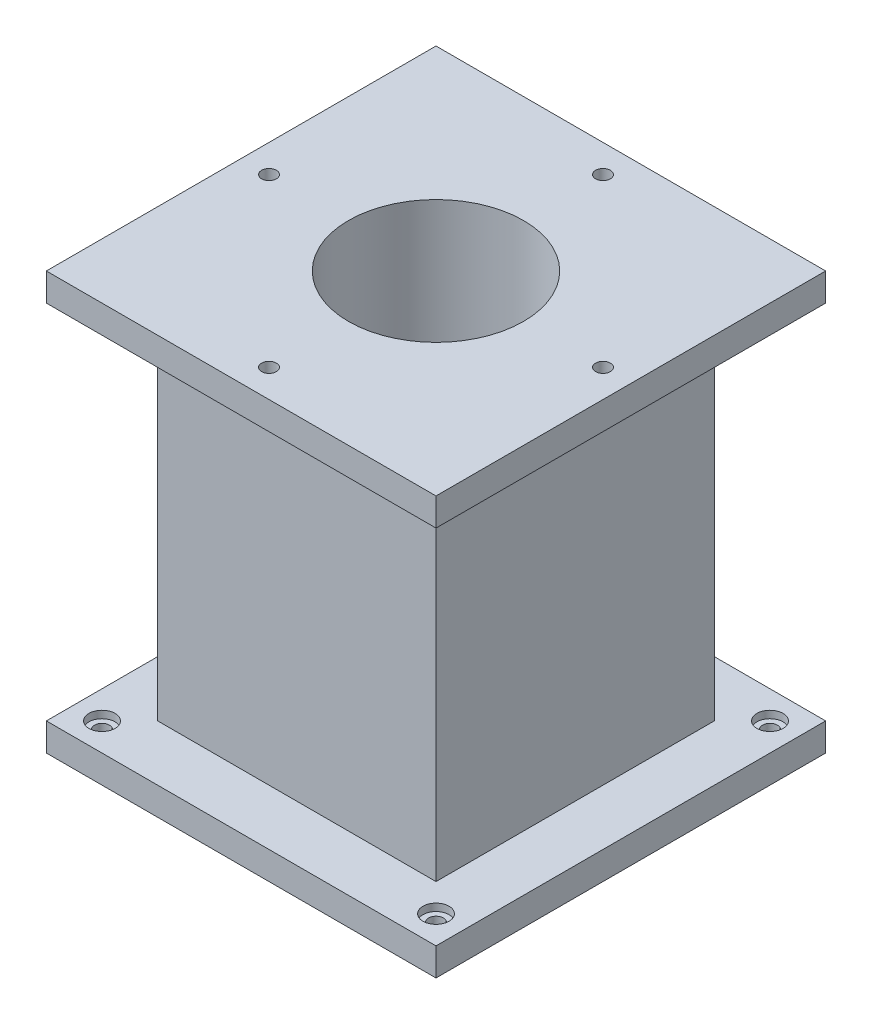
SolidWorks part; units mm, degrees
ref_plane "Front Plane" through (0, 0, 0) normal (0, 0, 1) x (1, 0, 0)
ref_plane "Top Plane" through (0, 0, 0) normal (0, 1, 0) x (1, 0, 0)
ref_plane "Right Plane" through (0, 0, 0) normal (1, 0, 0) x (0, 0, -1)
sketch "Sketch1" plane through (0, 0, 0) normal (0, 1, 0) x (1, 0, 0)
  line L1 (-88.9, -88.9) -> (88.9, -88.9)
  line L2 (-88.9, -88.9) -> (-88.9, 88.9)
  line L3 (-88.9, 88.9) -> (88.9, 88.9)
  line L4 (88.9, -88.9) -> (88.9, 88.9)
  line L5 (-88.9, -88.9) -> (88.9, 88.9) construction
  line L6 (-88.9, 88.9) -> (88.9, -88.9) construction
  point P0 (0, 0)
  dimension "D1" = 177.8
extrude "Boss-Extrude1" add sketch "Sketch1" along normal blind 12.7
sketch "Sketch2" plane through (0, 12.7, 0) normal (0, 1, 0) x (1, 0, 0)
  line L0 (88.9, 88.9) -> (-88.9, 88.9) construction
  line L1 (88.9, -88.9) -> (88.9, 88.9) construction
  point P0 (76.2, 76.2)
  dimension "D1" = 12.7
  dimension "D2" = 12.7
pattern_linear "LPattern1" count 2 spacing 177.8 along (0, 1, 0) of bodies 101 104
hole_wizard "CBORE for 1/4 Button Head Cap Screw1" positions "Sketch3" profile "Sketch5" counterbore size "1/4" standard "ANSI Inch" end condition through all
sketch "Sketch3" plane through (0, 12.7, 0) normal (0, 1, 0) x (1, 0, 0)
  point P0 (76.2, 76.2)
sketch "Sketch5" plane through (76.2, 12.7, -76.2) normal (1, 0, 0) x (0, 0, 1)
  line L0 (0, 0) -> (0, 12.7)
  line L1 (0, 12.7) -> (3.3782, 12.7)
  line L3 (3.3782, 12.7) -> (3.3782, 3.3528)
  line L4 (3.3782, 3.3528) -> (5.9538, 3.3528)
  line L5 (5.9538, 3.3528) -> (5.9538, 0)
  line L7 (5.9538, 0) -> (0, 0)
  line L11 (0, -6.35) -> (0, 107.95) construction
  dimension "Thru Hole Dia." = 6.7564
  dimension "Thru Hole Depth" = 12.7
  dimension "C'Bore Dia." = 11.9075
  dimension "C'Bore Depth" = 3.3528
ref_axis "Axis1" through (0, -0.635, 0) along (0, 1, 0)
pattern_circular "CirPattern1" count 4 over 360 about axis through (0, -0.635, 0) along (0, 1, 0) of "CBORE for 1/4 Button Head Cap Screw1"
sketch "Sketch6" plane through (0, 177.8, 0) normal (0, -1, 0) x (1, 0, 0)
  line L0 (88.9, 0) -> (46.7985, 0) construction
  line L1 (88.9, 88.9) -> (88.9, -88.9) construction
  point P0 (76.2, 0)
  dimension "D1" = 12.7
hole_wizard "CBORE for 1/4 Button Head Cap Screw2" positions "Sketch9" profile "Sketch10" counterbore size "1/4" standard "ANSI Inch" end condition through all
sketch "Sketch9" plane through (0, 177.8, 0) normal (0, -1, 0) x (-1, 0, 0)
  point P0 (-76.2, 0)
sketch "Sketch10" plane through (76.2, 177.8, 0) normal (1, 0, 0) x (0, 0, -1)
  line L0 (0, 0) -> (0, 12.7)
  line L1 (0, 12.7) -> (3.3782, 12.7)
  line L3 (3.3782, 12.7) -> (3.3782, 3.3528)
  line L4 (3.3782, 3.3528) -> (5.9538, 3.3528)
  line L5 (5.9538, 3.3528) -> (5.9538, 0)
  line L7 (5.9538, 0) -> (0, 0)
  line L11 (0, -6.35) -> (0, 107.95) construction
  dimension "Thru Hole Dia." = 6.7564
  dimension "Thru Hole Depth" = 12.7
  dimension "C'Bore Dia." = 11.9075
  dimension "C'Bore Depth" = 3.3528
pattern_circular "CirPattern2" count 4 over 360 about axis through (0, -0.635, 0) along (0, 1, 0) of "CBORE for 1/4 Button Head Cap Screw2"
sketch "Sketch11" plane through (0, 12.7, 0) normal (0, 1, 0) x (1, 0, 0)
  line L0 (88.9, 88.9) -> (-88.9, 88.9) construction
  line L1 (63.5, -63.5) -> (-63.5, -63.5)
  line L2 (63.5, -63.5) -> (63.5, 63.5)
  line L3 (63.5, 63.5) -> (-63.5, 63.5)
  line L4 (-63.5, -63.5) -> (-63.5, 63.5)
  line L5 (63.5, -63.5) -> (-63.5, 63.5) construction
  line L6 (63.5, 63.5) -> (-63.5, -63.5) construction
  point P0 (0, 0)
  dimension "D1" = 25.4
extrude "Boss-Extrude2" add sketch "Sketch11" along normal up to next
sketch "Sketch12" plane through (0, 190.5, 0) normal (0, 1, 0) x (1, 0, 0)
  circle A0 centre (0, 0) radius 39.9253
extrude "Cut-Extrude1" cut sketch "Sketch12" against normal through all
